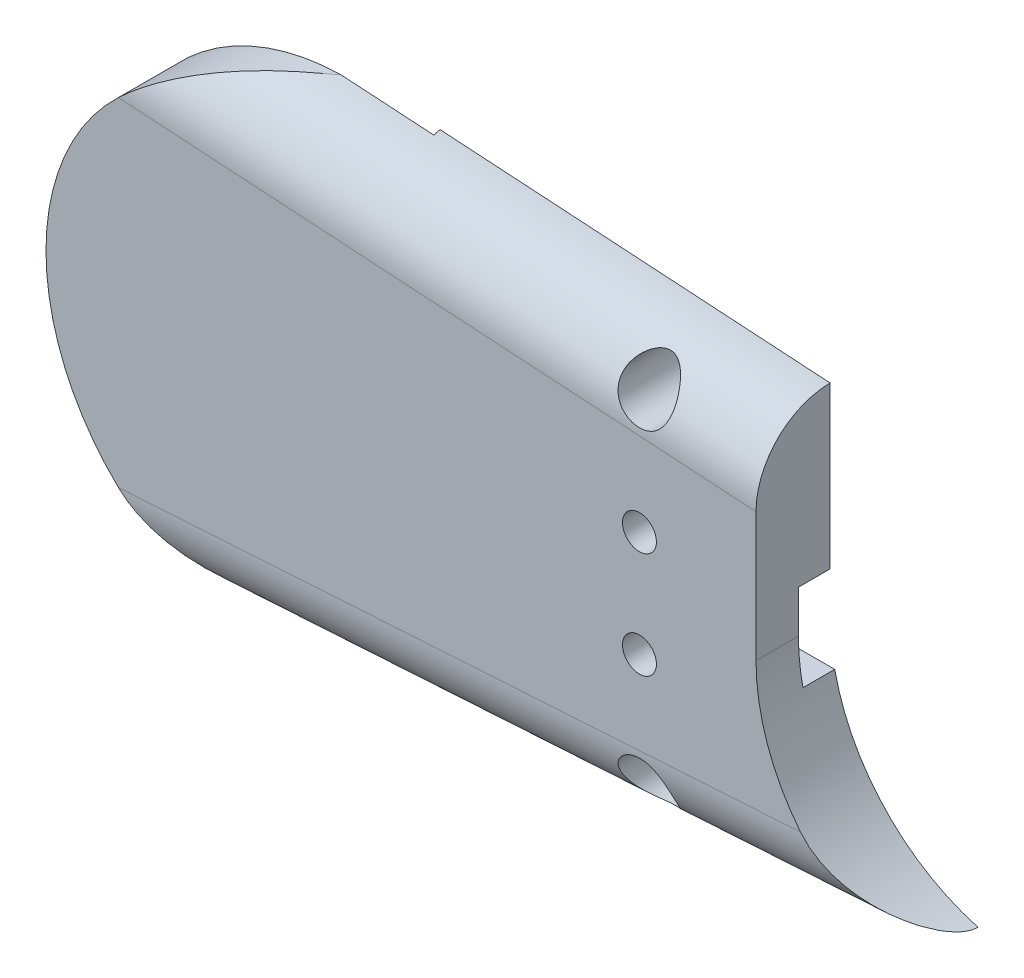
SolidWorks part; units mm, degrees
ref_plane "Front" through (0, 0, 0) normal (0, 0, 1) x (1, 0, 0)
ref_plane "Top" through (0, 0, 0) normal (0, 1, 0) x (1, 0, 0)
ref_plane "Right" through (0, 0, 0) normal (1, 0, 0) x (0, 0, -1)
sketch "Sketch1" plane through (0, 0, 0) normal (0, 0, 1) x (1, 0, 0)
  line L0 (0, 0) -> (-32, 0) construction
  line L2 (-32, 11) -> (-2.5264, 9.1579)
  line L3 (-32, -11) -> (-2.5264, -9.1579)
  line L4 (-9.5, 0) -> (-9.5, 9.5938)
  circle A0 centre (0, 0) radius 9.5
  circle A1 centre (-32, 0) radius 11
  circle A2 centre (0, 0) radius 9
extrude "Boss-Extrude1" add sketch "Sketch1" along normal blind 3.5 contours L2 A1 L3 | A1 L3 A0 L2 | L0 A1 L3 region at (-16.0478, -0.4531, 0) region at (-32.0001, 0, 0)
sketch "Sketch8" plane through (0, 0, 0) normal (0, 0, 1) x (1, 0, 0)
  line L0 (-20.5, 0) -> (-20.5, -11.5)
  line L1 (-20.5, -11.5) -> (-32, -11.5)
  circle A0 centre (-32, 0) radius 11.5
extrude "Joint Hole" cut sketch "Sketch8" along normal blind 0.35 contours A0 | A0 L1 L0 region at (-32, 0, 0) region at (-23.0687, -8.9313, 0)
sketch "Sketch3" plane through (0, 0, 0) normal (0, 0, 1) x (1, 0, 0)
  circle A0 centre (-32, 0) radius 7
extrude "Joint Insert" add sketch "Sketch3" against normal blind 3.25 from offset 0.35
sketch "Sketch4" plane through (0, 0, 0) normal (0, 0, 1) x (1, 0, 0)
  circle A0 centre (-32, 0) radius 8
  circle A1 centre (-32, 0) radius 7
extrude "Friction" add sketch "Sketch4" against normal blind 0.25 from offset 0.35
sketch "Sketch6" plane through (0, 0, 0) normal (1, 0, 0) x (0, 0, -1)
  line L0 (0, 0) -> (-1.5, 0) construction
  line L2 (-1.5, 0) -> (-1.5, 2)
  line L3 (-1.5, 2) -> (0, 2)
  line L4 (0, -9.1579) -> (0, 0) construction
  line L5 (-1.5, 0) -> (-1.5, -2)
  line L6 (-1.5, -2) -> (0, -2)
  line L7 (0, -8) -> (0, 8) construction
  arc A0 (0, 2) -> (0, -2) centre (0, 0) cw
extrude "Cut-Extrude2" cut sketch "Sketch6" against normal blind 43 contours A0 L3 L2 L5 L6 region at (0, 0, -0.0678)
sketch "Sketch7" plane through (0, 0, 0) normal (0, 1, 0) x (1, 0, 0)
  line L0 (-32, 0) -> (-32, -1.5) construction
  line L1 (-24.254, 0) -> (-39.746, 0) construction
  line L2 (-32, -3.5) -> (-32, -0.35) construction
  line L3 (-32, -1.5) -> (-30, -1.5)
  line L4 (-30, -1.5) -> (-30, 0)
  line L5 (-32, -1.5) -> (-43, -1.5)
  line L6 (-43, -1.5) -> (-43, 2)
  line L8 (-43, 2) -> (-32, 2)
  arc A0 (-30, 0) -> (-32, 2) centre (-32, 0) ccw
extrude "Cut-Extrude3" cut sketch "Sketch7" against normal blind 11 contours L5 L3 L4 region at (-36.6164, 0, -0.2249)
sketch "Sketch2" plane through (0, 0, 0) normal (0, 0, 1) x (1, 0, 0)
  line L0 (0, 0) -> (-15, 0) construction
  line L1 (-15, 0) -> (-15, 8) construction
  line L2 (-15, 0) -> (-15, -8) construction
  line L3 (-15, 0) -> (-15, 2.5) construction
  line L4 (-15, 0) -> (-15, -2.5) construction
  circle A0 centre (-15, 8) radius 0.8
  circle A1 centre (-15, -8) radius 0.8
  circle A2 centre (-15, 2.5) radius 0.8
  circle A3 centre (-15, -2.5) radius 0.8
extrude "Screw Holes" cut sketch "Sketch2" along normal through all
fillet "Fillet1" radius 3.5 2 edges at (-17.2632, -10.079, 3.5) (-20.75, 10.2969, 3.5)
sketch "Sketch9" plane through (0, 0, 0) normal (0, 0, 1) x (1, 0, 0)
  circle A0 centre (-15, 8) radius 1.25
  circle A1 centre (-15, -8) radius 1.25
extrude "Cut-Extrude4" cut sketch "Sketch9" against normal blind 3 from offset 3.5
